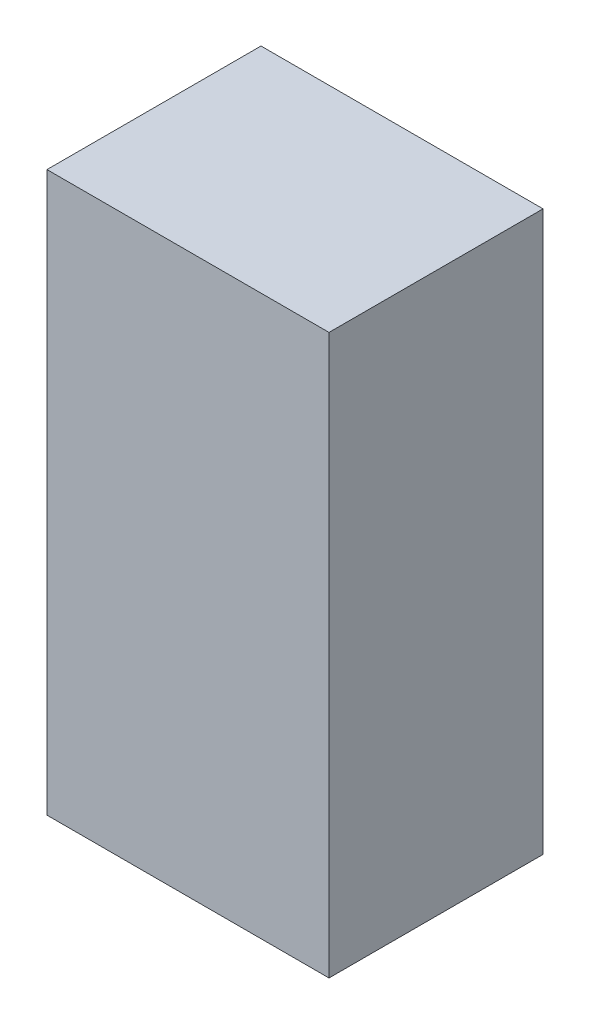
SolidWorks part; units mm, degrees
ref_plane "Plano frontal" through (0, 0, 0) normal (0, 0, 1) x (1, 0, 0)
ref_plane "Plano superior" through (0, 0, 0) normal (0, 1, 0) x (1, 0, 0)
ref_plane "Plano direito" through (0, 0, 0) normal (1, 0, 0) x (0, 0, -1)
sketch "Esboço1" plane through (0, 0, 0) normal (0, 0, 1) x (1, 0, 0)
  line L1 (-85, -168.5) -> (85, -168.5)
  line L2 (-85, -168.5) -> (-85, 168.5)
  line L3 (-85, 168.5) -> (85, 168.5)
  line L4 (85, -168.5) -> (85, 168.5)
  line L5 (-85, -168.5) -> (85, 168.5) construction
  line L6 (-85, 168.5) -> (85, -168.5) construction
  line L7 (-75, -158.5) -> (75, -158.5)
  line L8 (-75, -158.5) -> (-75, 158.5)
  line L9 (-75, 158.5) -> (75, 158.5)
  line L10 (75, -158.5) -> (75, 158.5)
  line L11 (-75, -158.5) -> (75, 158.5) construction
  line L12 (-75, 158.5) -> (75, -158.5) construction
  point P0 (0, 0)
  point P6 (0, 0)
  point P11 (0, 0)
  point P12 (0, 0)
  dimension "D1" = 337
  dimension "D2" = 170
  dimension "D3" = 10
  dimension "D4" = 10
extrude "Ressalto-extrusão1" add sketch "Esboço1" along normal blind 129 contours L2 L3 L4 L1
extrude "Corte-extrusão2" cut sketch "Esboço1<5>" along normal blind 128 contours L7 L10 L9 L8 region at (0, 0, 0)
sketch "Esboço1<5>" plane through (0, 0, 0) normal (0, 0, 1) x (1, 0, 0) same geometry as "Esboço1"
